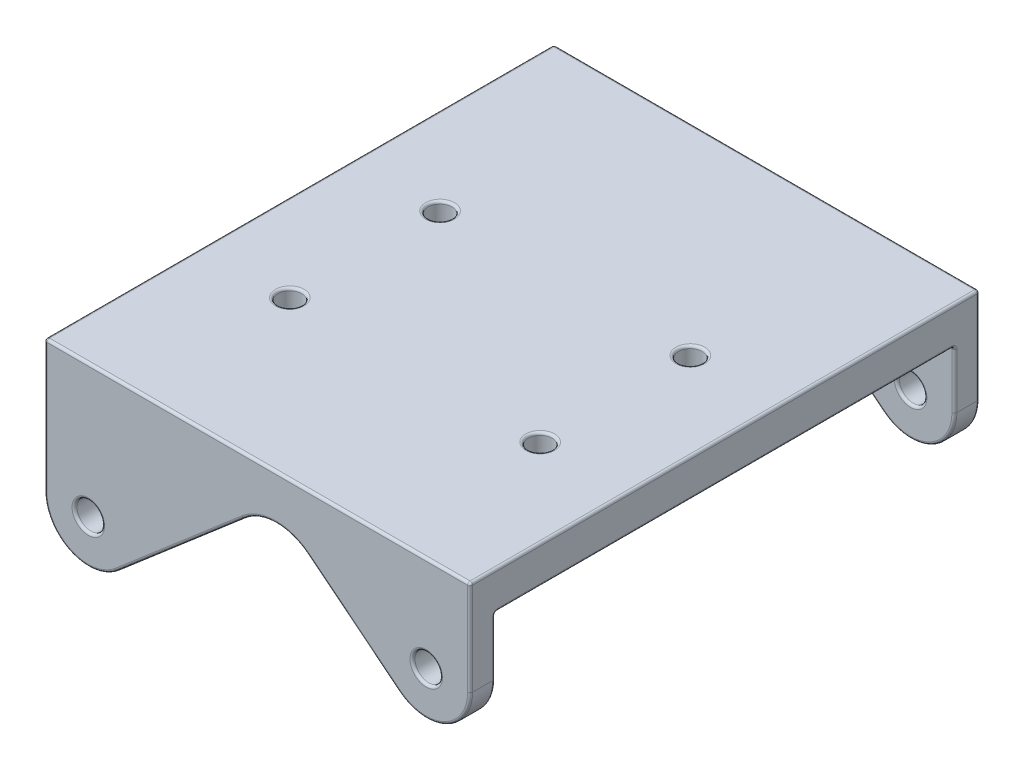
SolidWorks part; units mm, degrees
ref_plane "정면" through (0, 0, 0) normal (0, 0, 1) x (1, 0, 0)
ref_plane "윗면" through (0, 0, 0) normal (0, 1, 0) x (1, 0, 0)
ref_plane "우측면" through (0, 0, 0) normal (1, 0, 0) x (0, 0, -1)
sketch "스케치1" plane through (0, 0, 0) normal (0, 0, 1) x (1, 0, 0)
  line L0 (-18.5, -3) -> (-18.5, 7.6)
  line L1 (-18.5, 7.6) -> (15.5, 7.6)
  line L2 (15.5, 7.6) -> (15.5, 0)
  line L3 (-18.5, 4.6) -> (15.5, 4.6)
  line L4 (-12.7191, -5.6547) -> (-2.6068, 3.0339)
  line L5 (9.8125, -2.7322) -> (2.5, 3.1225)
  arc A0 (2.5, 3.1225) -> (-2.6068, 3.0339) centre (0, 0) ccw
  arc A1 (9.8125, -2.7322) -> (15.5, 0) centre (12, 0) ccw
  arc A2 (-18.5, -3) -> (-12.7191, -5.6547) centre (-15, -3) ccw
  circle A3 centre (-15, -3) radius 1.1
  circle A4 centre (12, 0) radius 1.1
  dimension "D1" = 8
  dimension "D2" = 7
  dimension "D3" = 7
  dimension "D9" = 2.2
  dimension "D4" = 12
  dimension "D5" = 15
  dimension "D6" = 3
  dimension "D7" = 10.6
  dimension "D8" = 3
extrude "보스-돌출1" add sketch "스케치1" along normal blind 2 contours L0 A2 L4 A0 L5 A1 L2 L3 A4 A3 | L0 L3 L2 L1 region at (-18.1423, 0.8, 0) region at (-1.5, 6.1, 0)
extrude "보스-돌출2" add sketch "스케치1<3>" against normal blind 18.35 contours L0 L3 L2 L1 region at (-1.5, 6.1, 0)
sketch "스케치1<3>" plane through (0, 0, 0) normal (0, 0, 1) x (1, 0, 0) same geometry as "스케치1"
mirror "대칭 복사1" about plane through (0, 0, -18.35) normal (0, 0, 1) of bodies 102
sketch "스케치2" plane through (0, 7.6, 0) normal (0, 1, 0) x (1, 0, 0)
  line L0 (-18.5, -2) -> (15.5, -2) construction
  line L1 (-1.5, -2) -> (-1.5, 30.1796) construction
  circle A0 centre (8.5, 10.6) radius 0.95
  circle A1 centre (8.5, 22.6) radius 0.95
  circle A2 centre (-11.5, 22.6) radius 0.95
  circle A3 centre (-11.5, 10.6) radius 0.95
  point P10 (0, 0)
  dimension "D2" = 1.9
  dimension "D1" = 12.6
  dimension "D3" = 12
  dimension "D4" = 12
  dimension "D5" = 20
  dimension "D6" = 10
extrude "컷-돌출1" cut sketch "스케치2" against normal through all
fillet "필렛1" radius 0.2 52 edges at (-16.4606, -6.1807, 0) (-7.6629, -1.3104, 0) (-0.0694, 3.9994, 0) (6.1563, 0.1952, 0) (13.5155, -3.1549, 0) (15.5, 2.3, 0) (-18.5, 0.8, 0) (-13.9, -3, 0) (13.1, 0, 0) (15.5, 2.3, -36.7) (13.5155, -3.1549, -36.7) (6.1563, 0.1952, -36.7) (-0.0694, 3.9994, -36.7) (-7.6629, -1.3104, -36.7) (-16.4606, -6.1807, -36.7) (-18.5, 0.8, -36.7) (-13.9, -3, -36.7) (13.1, 0, -36.7) (-16.4606, -6.1807, -38.7) (-7.6629, -1.3104, -38.7) (-0.0694, 3.9994, -38.7) (6.1563, 0.1952, -38.7) (13.5155, -3.1549, -38.7) (15.5, 3.8, -38.7) (-18.5, 2.3, -38.7) (-13.9, -3, -38.7) (13.1, 0, -38.7) (15.5, 4.6, -18.35) (-1.5, 4.6, -36.7) (-18.5, 4.6, -18.35) (-1.5, 4.6, 0) (8.5, 4.6, -11.55) (8.5, 4.6, -23.55) (-11.5, 4.6, -23.55) (-11.5, 4.6, -11.55) (15.5, 3.8, 2) (13.5155, -3.1549, 2) (6.1563, 0.1952, 2) (-0.0694, 3.9994, 2) (-7.6629, -1.3104, 2) (-16.4606, -6.1807, 2) (-18.5, 2.3, 2) (-13.9, -3, 2) (13.1, 0, 2) (-1.5, 7.6, 2) (-18.5, 7.6, -18.35) (-1.5, 7.6, -38.7) (15.5, 7.6, -18.35) (8.5, 7.6, -9.65) (8.5, 7.6, -21.65) (-11.5, 7.6, -21.65) (-11.5, 7.6, -9.65)
